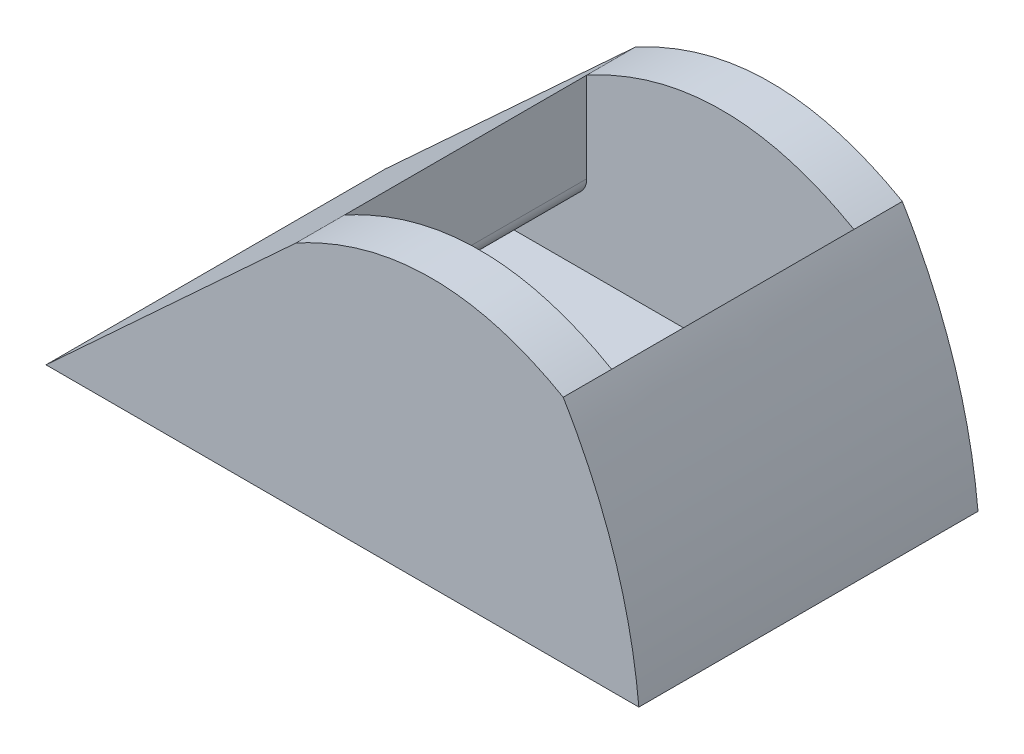
SolidWorks part; units mm, degrees
ref_plane "Alzado" through (0, 0, 0) normal (0, 0, 1) x (1, 0, 0)
ref_plane "Planta" through (0, 0, 0) normal (0, 1, 0) x (1, 0, 0)
ref_plane "Vista lateral" through (0, 0, 0) normal (1, 0, 0) x (0, 0, -1)
sketch "Sketch5" plane through (0, 0, 0) normal (0, 0, 1) x (1, 0, 0)
  line L0 (0, 0) -> (672.1713, 0)
  line L6 (263.9, 351.7684) -> (263.9, 166.523)
  line L7 (242.9237, 131.3363) -> (0, 0)
  line L10 (818.0053, 318.2236) -> (709.6757, 26.0924)
  arc A1 (815.3488, 351.7684) -> (818.0053, 318.2236) centre (780.5009, 332.1312) cw
  arc A2 (672.1713, 0) -> (709.6757, 26.0924) centre (672.1713, 40) ccw
  arc A3 (263.9, 166.523) -> (242.9237, 131.3363) centre (223.9, 166.523) cw
  spline S3 degree 2 poles (263.9, 351.7684) (546.1113, 505.6949) (815.3488, 351.7684) knots 0 0 0 1 1 1
  point P24 (700, 0)
  point P27 (263.9, 142.6772)
  dimension "D7" = 700
  dimension "D8" = 300
sketch "Sketch6" plane through (0, 0, 0) normal (0, 0, 1) x (1, 0, 0)
  line L13 (971.5099, -124.0751) -> (-252.2034, -124.0751)
  line L14 (-252.2034, -124.0751) -> (263.9, 351.7684)
  spline S0 degree 2 poles (815.3488, 351.7684) (947.5108, 130.3213) (971.5099, -124.0751) knots 0 0 0 1 1 1
  spline S1 degree 2 poles (263.9, 351.7684) (546.1113, 505.6949) (815.3488, 351.7684) knots 0 0 0 1 1 1
extrude "Boss-Extrude1" add sketch "Sketch6" along normal blind 350 and the other way blind 350
extrude "Cut-Extrude1" cut sketch "Sketch5" against normal blind 250 and the other way blind 250
